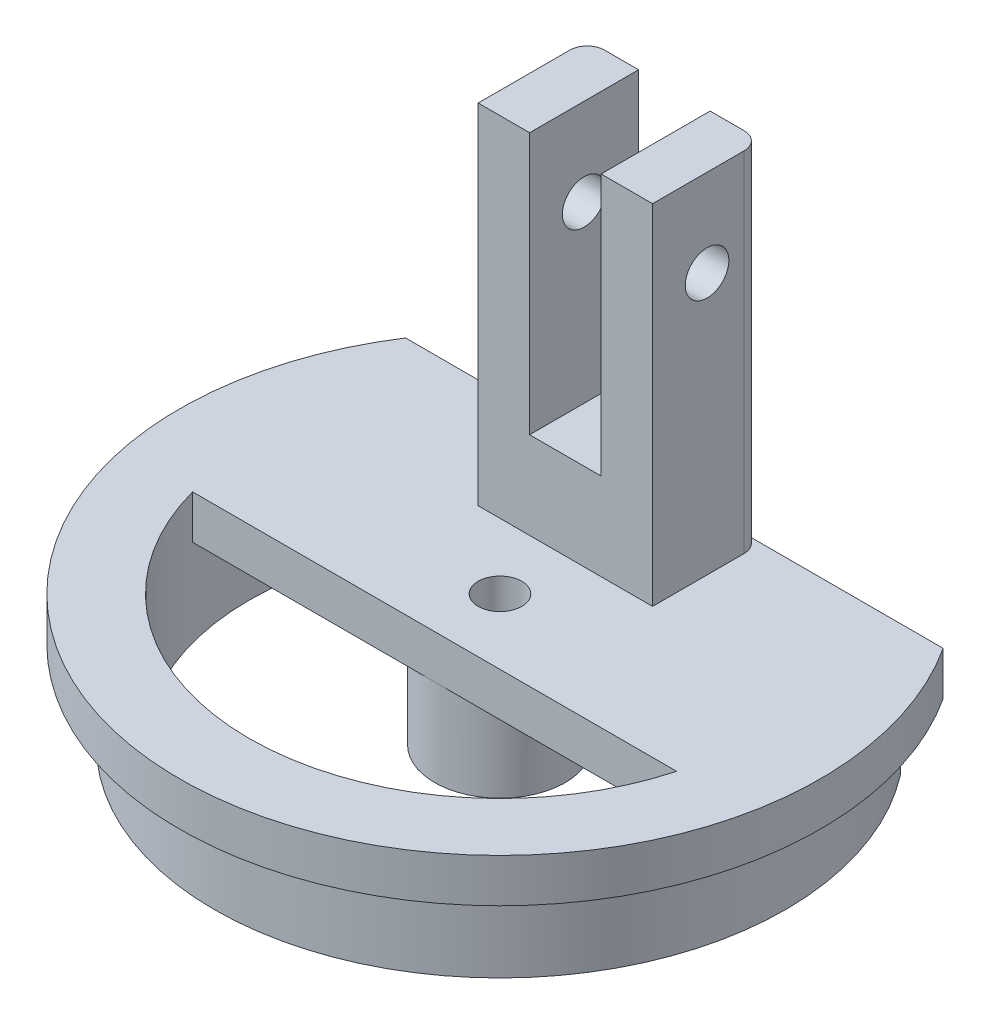
SolidWorks part; units mm, degrees
ref_plane "Спереди" through (0, 0, 0) normal (0, 0, 1) x (1, 0, 0)
ref_plane "Сверху" through (0, 0, 0) normal (0, 1, 0) x (1, 0, 0)
ref_plane "Справа" through (0, 0, 0) normal (1, 0, 0) x (0, 0, -1)
sketch "Эскиз1" plane through (0, 0, 0) normal (0, 1, 0) x (1, 0, 0)
  circle A0 centre (0, 0) radius 2.5
  circle A1 centre (0, 0) radius 7.5
  dimension "D1" = 15
  dimension "D2" = 5
extrude "cylinder" add sketch "Эскиз1" along normal blind 5 and the other way blind 10
sketch "Эскиз2" plane through (0, 0, 0) normal (0, 1, 0) x (1, 0, 0)
  circle A0 centre (0, 0) radius 36.75
  circle A1 centre (0, 0) radius 2.5
  dimension "D1" = 73.5
  dimension "D2" = 5
extrude "base horizont" add sketch "Эскиз2" along normal blind 5
sketch "Эскиз3" plane through (0, 5, 0) normal (0, 1, 0) x (1, 0, 0)
  circle A0 centre (0, 0) radius 28.75
  circle A1 centre (0, 0) radius 32.75
  dimension "D1" = 57.5
  dimension "D2" = 65.5
extrude "edge" add sketch "Эскиз3" against normal blind 15
sketch "Эскиз4" plane through (0, 5, 0) normal (0, 1, 0) x (1, 0, 0)
  line L1 (-10, 2.5) -> (10, 2.5)
  line L2 (-10, 2.5) -> (-10, 20)
  line L3 (-10, 20) -> (10, 20)
  line L4 (10, 2.5) -> (10, 20)
  circle A1 centre (0, 0) radius 2.5 construction
  point P4 (0, 2.5)
  dimension "D1" = 20
  dimension "D2" = 20
extrude "rectangle" add sketch "Эскиз4" along normal blind 40 and the other way up to surface (15 mm away) other way up to face at (0, -10, 28.75)
sketch "Эскиз6" plane through (0, 45, 0) normal (0, 1, 0) x (1, 0, 0)
  line L0 (10, 20) -> (-10, 20) construction
  line L1 (-4.1, 20) -> (4.1, 20)
  line L2 (-4.1, 20) -> (-4.1, 2.5)
  line L3 (-4.1, 2.5) -> (4.1, 2.5)
  line L4 (4.1, 20) -> (4.1, 2.5)
  line L6 (0, 0) -> (0, -39.8296) construction
  line L7 (-10, 2.5) -> (10, 2.5) construction
  point P9 (0, 20)
  dimension "D1" = 8.2
extrude "Вытянуть5" cut sketch "Эскиз6" against normal blind 30
sketch "Эскиз7" plane through (10, 0, 0) normal (1, 0, 0) x (0, 0, -1)
  line L4 (20, 45) -> (20, 5) construction
  line L5 (2.5, 45) -> (20, 45) construction
  circle A0 centre (13.75, 35) radius 2.5
  dimension "D3" = 5
  dimension "D1" = 6.25
  dimension "D2" = 10
extrude "Вытянуть6" cut sketch "Эскиз7" against normal up to surface (20 mm away) up to face at (-10, 25, -11.25)
sketch "Эскиз8" plane through (0, 0, 0) normal (0, 1, 0) x (1, 0, 0)
  line L1 (-30.8312, 36.75) -> (30.8312, 36.75)
  line L2 (-30.8312, 36.75) -> (-30.8312, 20)
  line L3 (-30.8312, 20) -> (30.8312, 20)
  line L4 (30.8312, 36.75) -> (30.8312, 20)
  circle A1 centre (0, 0) radius 36.75 construction
  dimension "D1" = 20
extrude "Вытянуть7" cut sketch "Эскиз8" along normal up to next and the other way up to next
sketch "Эскиз9" plane through (0, 45, 0) normal (0, 1, 0) x (1, 0, 0)
  line L0 (10, 2.5) -> (10, 20) construction
  line L1 (-10, 2.5) -> (10, 2.5)
  line L2 (-10, 2.5) -> (-10, 7.5)
  line L3 (-10, 7.5) -> (10, 7.5)
  line L4 (10, 2.5) -> (10, 7.5)
  dimension "D2" = 5
extrude "Вытянуть8" cut sketch "Эскиз9" against normal up to surface (40 mm away) up to face at (0, 5, -3.5313)
sketch "Эскиз10" plane through (0, 5, 0) normal (0, 1, 0) x (1, 0, 0)
  line L0 (0, -7.5) -> (45.2157, -7.5) construction
  line L1 (-27.7545, -7.5) -> (27.7545, -7.5)
  arc A0 (-27.7545, -7.5) -> (27.7545, -7.5) centre (0, 0) ccw
  arc A3 (7.0711, 2.5) -> (-7.0711, 2.5) centre (0, 0) ccw construction
  arc A6 (-20.6534, 20) -> (20.6534, 20) centre (0, 0) ccw construction
extrude "pie" cut sketch "Эскиз10" against normal up to next
fillet "Скругление2" radius 2 2 edges at (-10, 25, -20) (10, 25, -20)
